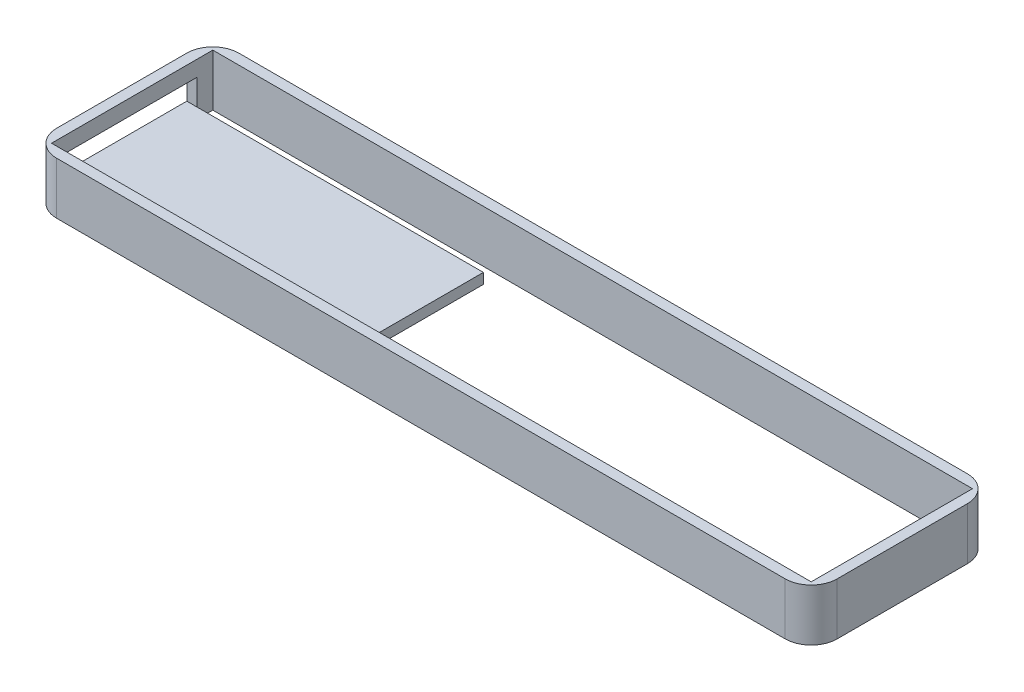
SolidWorks part; units mm, degrees
ref_plane "Front Plane" through (0, 0, 0) normal (0, 0, 1) x (1, 0, 0)
ref_plane "Top Plane" through (0, 0, 0) normal (0, 1, 0) x (1, 0, 0)
ref_plane "Right Plane" through (0, 0, 0) normal (1, 0, 0) x (0, 0, -1)
sketch "Sketch1" plane through (0, 0, 0) normal (0, 1, 0) x (1, 0, 0)
  line L0 (-75, 0) -> (75, 1.0074) construction
  line L1 (-75, -17.5) -> (75, -17.5)
  line L2 (-75, -17.5) -> (-75, 17.5)
  line L3 (-75, 17.5) -> (75, 17.5)
  line L4 (75, -17.5) -> (75, 17.5)
  line L5 (-75, -17.5) -> (75, 17.5) construction
  line L6 (-75, 17.5) -> (75, -17.5) construction
  line L8 (-73, -15.5) -> (73, -15.5)
  line L9 (-73, -15.5) -> (-73, 15.5)
  line L10 (-73, 15.5) -> (73, 15.5)
  line L11 (73, -15.5) -> (73, 15.5)
  line L12 (-73, -15.5) -> (73, 15.5) construction
  line L13 (-73, 15.5) -> (73, -15.5) construction
  line L14 (-73, 12.5) -> (-18, 12.5)
  line L15 (-73, 12.5) -> (-73, -12.5)
  line L16 (-73, -12.5) -> (-18, -12.5)
  line L17 (-18, 12.5) -> (-18, -12.5)
  point P0 (0, 0)
  point P8 (0, 0)
  dimension "D1" = 150
  dimension "D2" = 35
  dimension "D3" = 146
  dimension "D4" = 31
  dimension "D5" = 25
  dimension "D6" = 55
  dimension "D7" = 3
extrude "Boss-Extrude1" add sketch "Sketch1" along normal blind 10 contours L1 L4 L3 L2 L11 L8 L9 L10 | L17 L14 L9 L16
sketch "Sketch2" plane through (0, 10, 0) normal (0, 1, 0) x (1, 0, 0)
  line L1 (-73, 12.5) -> (-18, 12.5)
  line L2 (-73, 12.5) -> (-73, -12.5)
  line L3 (-73, -12.5) -> (-18, -12.5)
  line L4 (-18, 12.5) -> (-18, -12.5)
extrude "Cut-Extrude3" cut sketch "Sketch2" against normal blind 8
sketch "Sketch6" plane through (-75, 0, 0) normal (-1, 0, 0) x (0, 0, 1)
  line L0 (-17.5, 10) -> (-17.5, 0) construction
  line L1 (-12.5, 7) -> (12.5, 7)
  line L2 (-12.5, 7) -> (-12.5, 2)
  line L3 (-12.5, 2) -> (12.5, 2)
  line L4 (12.5, 7) -> (12.5, 2)
  line L5 (17.5, 0) -> (-17.5, 0) construction
  dimension "D1" = 5
  dimension "D2" = 25
  dimension "D3" = 2
  dimension "D4" = 5
extrude "Cut-Extrude4" cut sketch "Sketch6" against normal blind 8
fillet "Fillet1" radius 5 4 edges at (75, 5, -17.5) (75, 5, 17.5) (-75, 5, -17.5) (-75, 5, 17.5)
